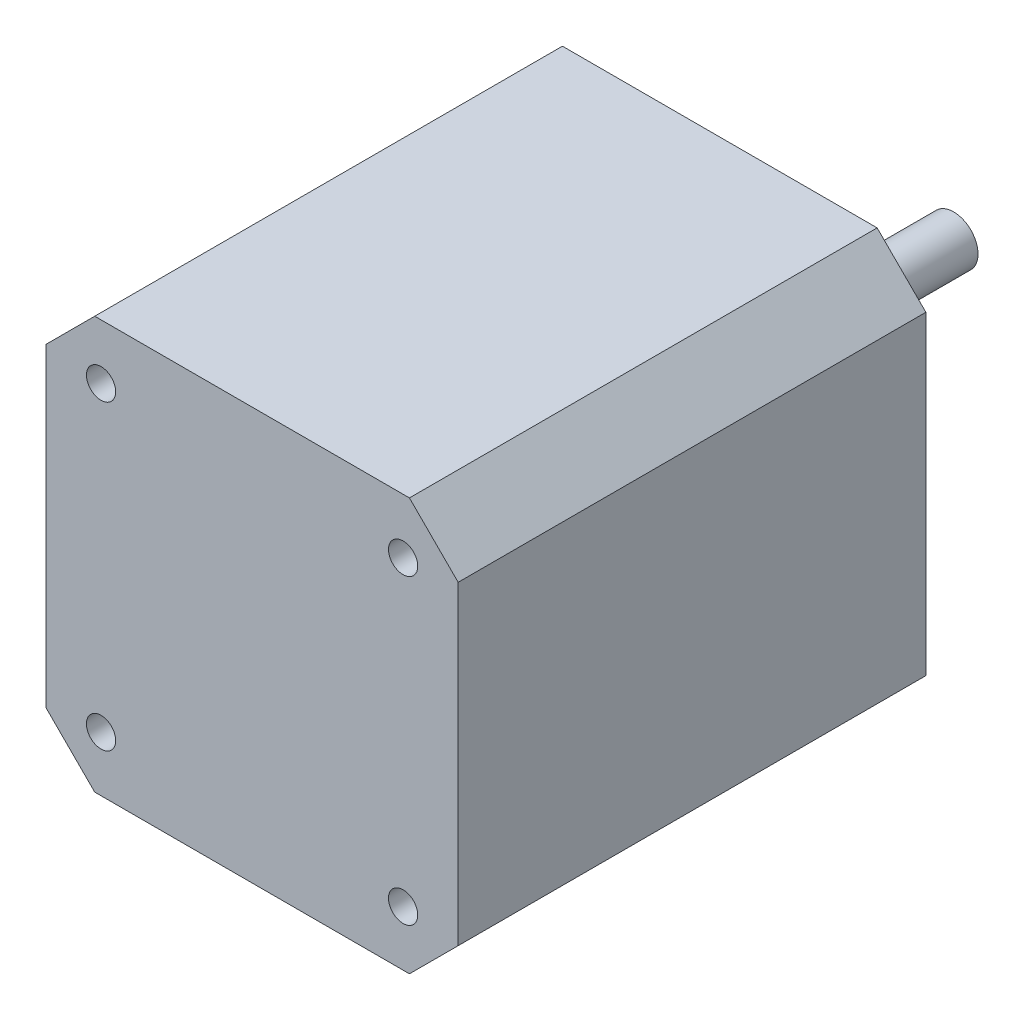
SolidWorks part; units mm, degrees
ref_plane "Front Plane" through (0, 0, 0) normal (0, 0, 1) x (1, 0, 0)
ref_plane "Top Plane" through (0, 0, 0) normal (0, 1, 0) x (1, 0, 0)
ref_plane "Right Plane" through (0, 0, 0) normal (1, 0, 0) x (0, 0, -1)
sketch "Sketch1" plane through (0, 0, 0) normal (0, 0, 1) x (1, 0, 0)
  line L0 (-21.15, 16.15) -> (-16.15, 21.15)
  line L1 (-16.15, -21.15) -> (16.15, -21.15)
  line L2 (-21.15, -16.15) -> (-21.15, 16.15)
  line L3 (-16.15, 21.15) -> (16.15, 21.15)
  line L4 (21.15, -16.15) -> (21.15, 16.15)
  line L5 (-21.15, -21.15) -> (21.15, 21.15) construction
  line L6 (-21.15, 21.15) -> (21.15, -21.15) construction
  line L7 (-21.15, -16.15) -> (-16.15, -21.15)
  line L8 (16.15, -21.15) -> (21.15, -16.15)
  line L9 (16.15, 21.15) -> (21.15, 16.15)
  line L10 (-1.7678, 1.7678) -> (-1.7678, -1.7678)
  circle A0 centre (-15.5, 15.5) radius 1.5
  circle A1 centre (-15.5, -15.5) radius 1.5
  circle A2 centre (15.5, -15.5) radius 1.5
  circle A3 centre (15.5, 15.5) radius 1.5
  circle A4 centre (0, 0) radius 11
  arc A6 (-1.7678, 1.7678) -> (-1.7678, -1.7678) centre (0, 0) cw
  point P0 (0, 0)
  dimension "D2" = 3
  dimension "D4" = 22
  dimension "D5" = 2.5
  dimension "D1" = 42.3
  dimension "D3" = 31
extrude "Boss-Extrude1" add sketch "Sketch1" along normal blind 48 contours A1 | A0 | A3 | A2 | L1 L8 L4 L9 L3 L0 L2 L7
extrude "Boss-Extrude2" add sketch "Sketch1<5>" against normal blind 2 contours A4
sketch "Sketch1<5>" plane through (0, 0, 0) normal (0, 0, 1) x (1, 0, 0) same geometry as "Sketch1"
extrude "Boss-Extrude3" add sketch "Sketch1<6>" against normal blind 24 contours L10 A6
sketch "Sketch1<6>" plane through (0, 0, 0) normal (0, 0, 1) x (1, 0, 0) same geometry as "Sketch1"
